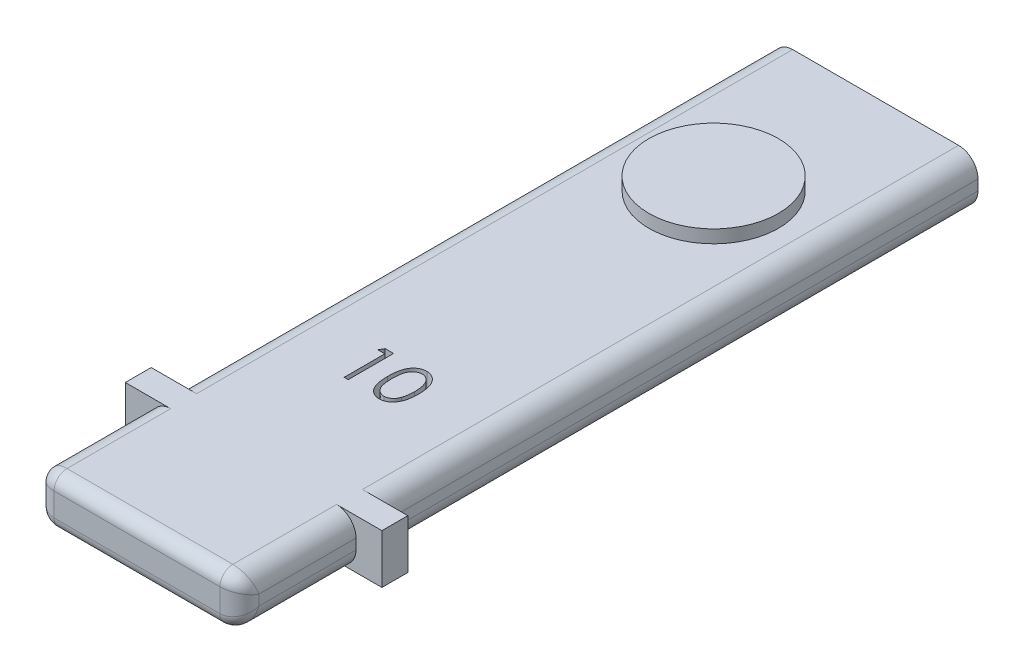
SolidWorks part; units mm, degrees
ref_plane "Front Plane" through (0, 0, 0) normal (0, 0, 1) x (1, 0, 0)
ref_plane "Top Plane" through (0, 0, 0) normal (0, 1, 0) x (1, 0, 0)
ref_plane "Right Plane" through (0, 0, 0) normal (1, 0, 0) x (0, 0, -1)
sketch "Sketch2" plane through (0, 0, 0) normal (0, 1, 0) x (1, 0, 0)
  line L1 (0, 0) -> (15.8, 0)
  line L2 (0, 0) -> (0, 57)
  line L3 (0, 57) -> (15.8, 57)
  line L4 (15.8, 0) -> (15.8, 57)
  dimension "D1" = 57
  dimension "D2" = 15.8
extrude "Boss-Extrude1" add sketch "Sketch2" along normal blind 3.8
fillet "Fillet3" radius 1 2 edges at (7.9, 0, 0) (7.9, 3.8, 0)
sketch "Sketch5" plane through (0, 3.8, 0) normal (0, 1, 0) x (1, 0, 0)
  line L0 (15.8, 57) -> (0, 57) construction
  circle A0 centre (7.9, 44.5) radius 5
  point P4 (7.9, 57)
  dimension "D1" = 10
  dimension "D2" = 12.5
extrude "Boss-Extrude4" add sketch "Sketch5" along normal blind 1
sketch "Sketch6" plane through (15.8, 0, 0) normal (1, 0, 0) x (0, 0, -1)
  line L0 (9, 3.8) -> (9, 0)
  line L1 (1, 3.8) -> (57, 3.8) construction
  line L2 (1, 0) -> (57, 0) construction
  line L3 (9, 0) -> (11, 0)
  line L4 (11, 0) -> (11, 3.8)
  line L5 (11, 3.8) -> (9, 3.8)
  line L6 (0, 2.8) -> (0, 1) construction
  dimension "D1" = 9
  dimension "D2" = 2
extrude "Boss-Extrude5" add sketch "Sketch6" along normal blind 2
sketch "Sketch7" plane through (0, 0, 0) normal (-1, 0, 0) x (0, 0, 1)
  line L0 (-57, 0) -> (-1, 0) construction
  line L1 (-9, 0) -> (-11, 0)
  line L2 (-9, 0) -> (-9, 3.8)
  line L3 (-9, 3.8) -> (-11, 3.8)
  line L4 (-11, 0) -> (-11, 3.8)
  line L5 (-57, 3.8) -> (-1, 3.8) construction
  line L6 (0, 2.8) -> (0, 1) construction
  dimension "D1" = 9
  dimension "D2" = 2
extrude "Boss-Extrude6" add sketch "Sketch7" along normal blind 2
fillet "Fillet4" radius 1.5 14 edges at (0, 0.2929, -0.2929) (0, 1.9, 0) (0, 3.5071, -0.2929) (15.8, 0.2929, -0.2929) (15.8, 1.9, 0) (15.8, 3.5071, -0.2929) (0, 0, -34) (0, 0, -5) (0, 3.8, -5) (0, 3.8, -34) (15.8, 0, -34) (15.8, 3.8, -34) (15.8, 0, -5) (15.8, 3.8, -5)
sketch "Sketch9" plane through (0, 3.8, 0) normal (0, 1, 0) x (1, 0, 0)
  text T0 "10\r\n"
extrude "Cut-Extrude1" cut sketch "Sketch9" against normal blind 5
